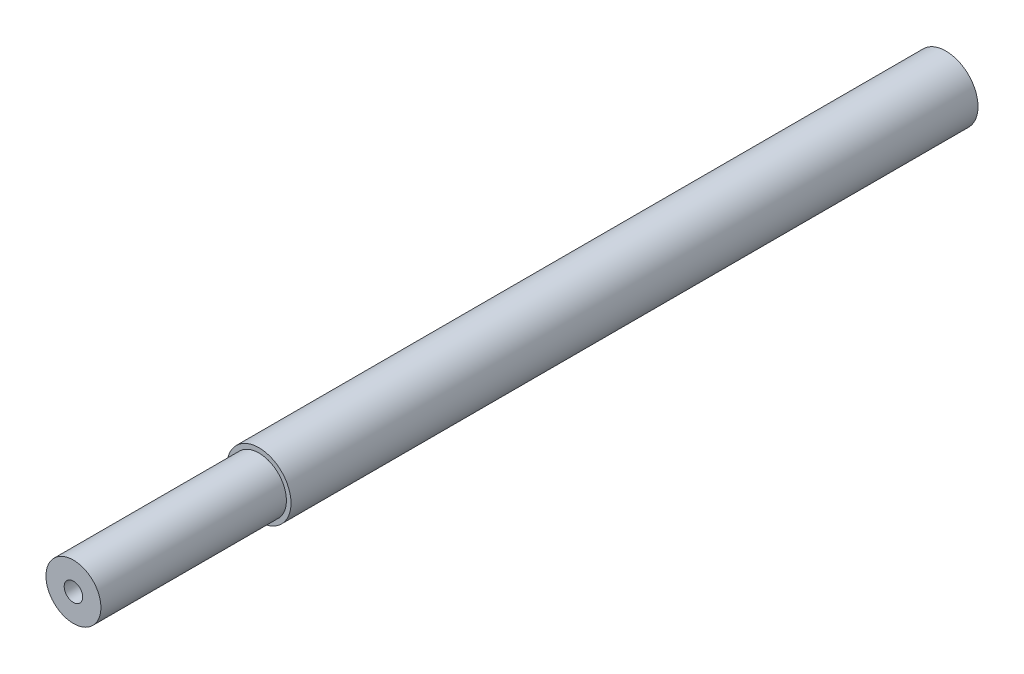
SolidWorks part; units mm, degrees
ref_plane "Front Plane" through (0, 0, 0) normal (0, 0, 1) x (1, 0, 0)
ref_plane "Top Plane" through (0, 0, 0) normal (0, 1, 0) x (1, 0, 0)
ref_plane "Right Plane" through (0, 0, 0) normal (1, 0, 0) x (0, 0, -1)
sketch "Sketch1" plane through (0, 0, 0) normal (1, 0, 0) x (0, 0, -1)
  line L0 (0, 0) -> (183, 0) construction
  line L1 (183, 0) -> (183, 7)
  line L3 (-7.5, 6) -> (-7.5, 0)
  line L4 (-7.5, 0) -> (183, 0)
  line L5 (-7.5, 6) -> (33, 6)
  line L6 (33, 6) -> (33, 7)
  line L7 (33, 7) -> (183, 7)
  line L8 (-8, 6) -> (-8, -6) construction
  line L9 (33, -12) -> (33, 12) construction
  line L10 (33, -50) -> (33, 50) construction
  point P9 (185.5552, 0)
  point P14 (186.1782, 0)
  point P17 (185.2003, 0)
  dimension "D1" = 12
  dimension "D2" = 0.5
  dimension "D3" = 14
  dimension "D4" = 150
revolve "Revolve1" add sketch "Sketch1" angle 360 about L0
sketch "Sketch2" plane through (0, 0, 7.5) normal (0, 0, 1) x (1, 0, 0)
  circle A0 centre (0, 0) radius 2.0193
  dimension "D1" = 4.0386
extrude "Cut-Extrude1" cut sketch "Sketch2" against normal blind 25
